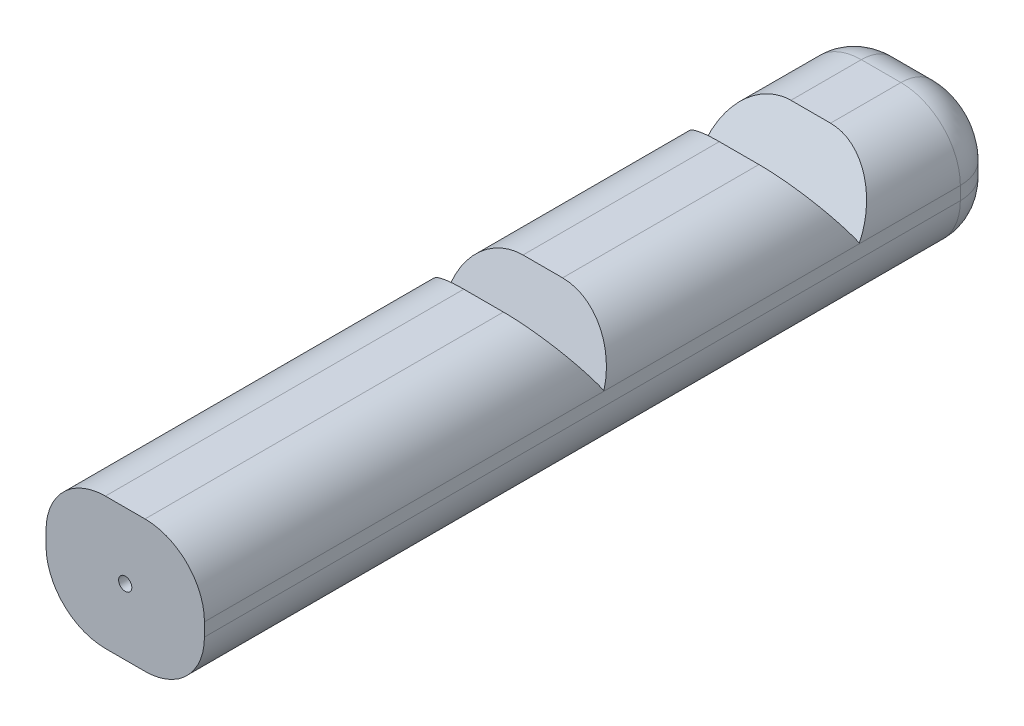
SolidWorks part; units mm, degrees
ref_plane "Front Plane" through (0, 0, 0) normal (0, 0, 1) x (1, 0, 0)
ref_plane "Top Plane" through (0, 0, 0) normal (0, 1, 0) x (1, 0, 0)
ref_plane "Right Plane" through (0, 0, 0) normal (1, 0, 0) x (0, 0, -1)
sketch "Sketch1" plane through (0, 0, 0) normal (1, 0, 0) x (0, 0, -1)
  line L0 (-24.5774, 0) -> (35.9238, 0)
  line L1 (35.9238, 0) -> (35.9238, 10)
  line L2 (35.9238, 10) -> (27.3434, 10)
  line L3 (27.3434, 10) -> (25.0261, 5.5532)
  line L4 (25.0261, 5.5532) -> (21.9183, 10)
  line L5 (21.9183, 10) -> (7.0511, 10)
  line L6 (7.0511, 10) -> (5.6732, 5.5532)
  line L7 (5.6732, 5.5532) -> (2.5654, 10)
  line L8 (2.5654, 10) -> (-24.5774, 10)
  line L9 (-24.5774, 10) -> (-24.5774, 0)
  line L10 (0, 13.9211) -> (0, -19.2105) construction
  line L11 (-24.5774, 0) -> (42.8759, 0) construction
  dimension "D2" = 27.1428
  dimension "D3" = 14.8672
  dimension "D4" = 8.5804
  dimension "D5" = 10
  dimension "D6" = 60.5012
  dimension "D7" = 4.4468
  dimension "D8" = 4.4468
  dimension "D9" = 4.4468
  dimension "D10" = 4.4468
  dimension "D11" = 0
  dimension "D12" = 5.4252
  dimension "D13" = 5.4252
  dimension "D14" = 24.5774
  dimension "D15" = 17.216
extrude "Boss-Extrude1" add sketch "Sketch1" along normal blind 12
sketch "Sketch2" plane through (0, 0, 24.5774) normal (0, 0, 1) x (1, 0, 0)
  line L0 (6, 10) -> (6, 0) construction
  line L1 (12, 10) -> (0, 10) construction
  line L2 (12, 0) -> (0, 0) construction
  circle A0 centre (6, 5) radius 0.5
  dimension "D1" = 1
extrude "Cut-Extrude1" cut sketch "Sketch2" against normal through all
fillet "Fillet1" radius 3.25 4 edges at (12, 5, -35.9238) (6, 0, -35.9238) (0, 5, -35.9238) (6, 10, -35.9238)
fillet "Fillet2" radius 4.5 12 edges at (11.0481, 0.9519, -34.9719) (0.9519, 0.9519, -34.9719) (11.0481, 9.0481, -34.9719) (0.9519, 9.0481, -34.9719) (12, 0, -4.0482) (0, 0, -4.0482) (12, 10, -30.0086) (12, 10, -14.4847) (12, 10, 11.006) (0, 10, 11.006) (0, 10, -14.4847) (0, 10, -30.0086)
